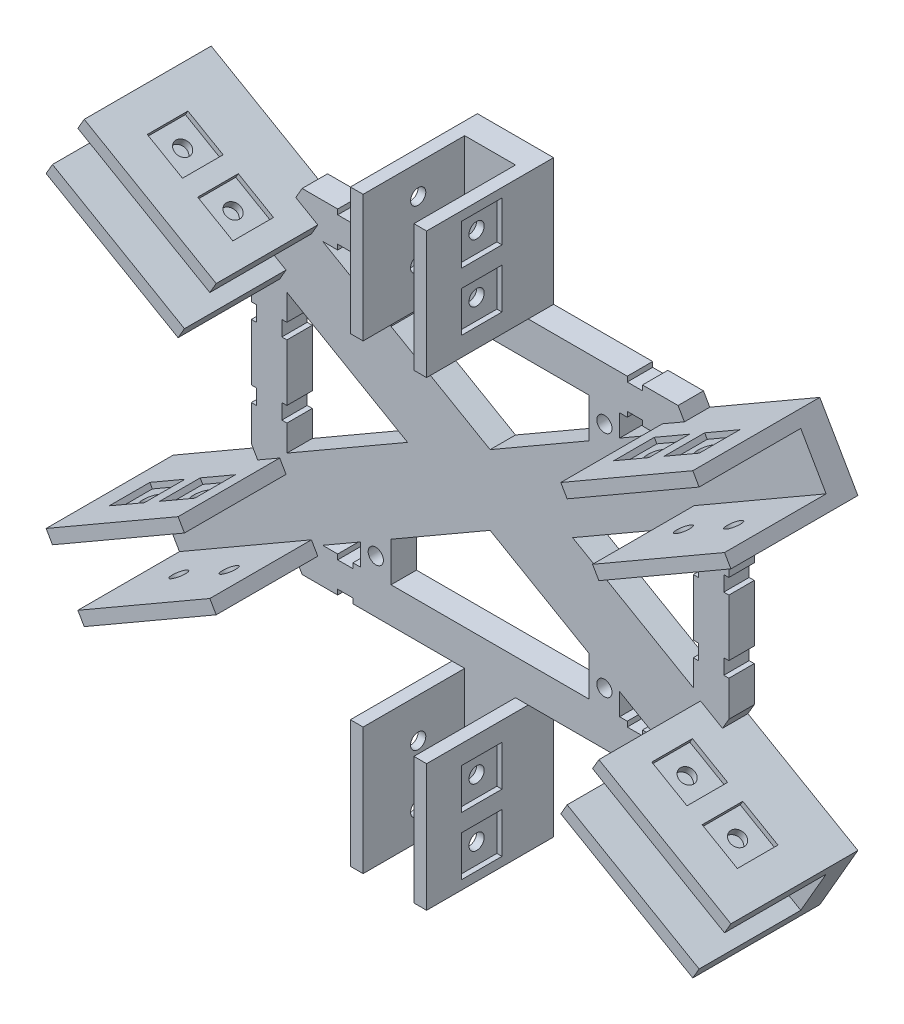
SolidWorks part; units mm, degrees
ref_plane "Plan de face" through (0, 0, 0) normal (0, 0, 1) x (1, 0, 0)
ref_plane "Plan de dessus" through (0, 0, 0) normal (0, 1, 0) x (1, 0, 0)
ref_plane "Plan de droite" through (0, 0, 0) normal (1, 0, 0) x (0, 0, -1)
sketch "Esquisse1" plane through (0, 0, 0) normal (0, 0, 1) x (1, 0, 0)
  line L1 (-27, -32.909) -> (-27, -31.909)
  line L2 (-27, -31.909) -> (-30, -31.909)
  line L3 (-30, -31.909) -> (-30, -32.909)
  line L4 (-30, -32.909) -> (-37, -32.909)
  line L5 (89.9983, 57.7339) -> (33.4379, 25.0787) construction
  line L6 (-47, -15.5885) -> (-47, -8.5885)
  line L7 (-47, -8.5885) -> (-46, -8.5885)
  line L8 (-46, -8.5885) -> (-46, -5.5885)
  line L9 (-46, -5.5885) -> (-47, -5.5885)
  line L10 (-47, -5.5885) -> (-47, 5.5885)
  line L11 (0, -32.909) -> (0, 32.909) construction
  line L12 (40, 0) -> (-40, 0) construction
  line L13 (-42, -24.2487) -> (0, 0) construction
  line L14 (-40, 5.5885) -> (-40, -5.5885)
  line L15 (-40, -5.5885) -> (-41, -5.5885)
  line L16 (-41, -5.5885) -> (-41, -8.5885)
  line L17 (-41, -8.5885) -> (-40, -8.5885)
  line L18 (-40, -8.5885) -> (-40, -13.7128)
  line L19 (40, 13.7128) -> (16.2487, 0)
  line L20 (-32.9585, -25.909) -> (-30, -25.909)
  line L21 (-30, -25.909) -> (-30, -26.909)
  line L22 (-30, -26.909) -> (-27, -26.909)
  line L23 (-27, -26.909) -> (-27, -25.909)
  line L24 (59.9007, 43.2438) -> (38.2501, 30.7438)
  line L25 (-42, 24.2487) -> (0, 0) construction
  line L26 (19.5, -25.909) -> (0, -25.909)
  line L27 (-27, 26.909) -> (-27, 25.909)
  line L28 (-30, 26.909) -> (-27, 26.909)
  line L29 (-30, 25.909) -> (-30, 26.909)
  line L30 (-32.9585, 25.909) -> (-30, 25.909)
  line L31 (-40, 13.7128) -> (-16.2487, 0)
  line L32 (-40, 8.5885) -> (-40, 13.7128)
  line L33 (-41, 8.5885) -> (-40, 8.5885)
  line L34 (-41, 5.5885) -> (-41, 8.5885)
  line L35 (-40, 5.5885) -> (-41, 5.5885)
  line L36 (-46, 5.5885) -> (-47, 5.5885)
  line L37 (-46, 8.5885) -> (-46, 5.5885)
  line L38 (-47, 8.5885) -> (-46, 8.5885)
  line L39 (-47, 15.5885) -> (-47, 8.5885)
  line L40 (-59.9007, 43.2438) -> (-38.2501, 30.7438)
  line L41 (-30, 32.909) -> (-37, 32.909)
  line L42 (-30, 31.909) -> (-30, 32.909)
  line L43 (-27, 31.909) -> (-30, 31.909)
  line L44 (-27, 32.909) -> (-27, 31.909)
  line L45 (-27, 32.909) -> (-7.5, 32.909)
  line L46 (42, 24.2487) -> (0, 0) construction
  line L47 (42, -24.2487) -> (0, 0) construction
  line L48 (27, 32.909) -> (27, 31.909)
  line L49 (27, 31.909) -> (30, 31.909)
  line L50 (30, 31.909) -> (30, 32.909)
  line L51 (30, 32.909) -> (37, 32.909)
  line L52 (-45.7501, 17.7534) -> (-47, 15.5885)
  line L53 (47, 15.5885) -> (47, 8.5885)
  line L54 (47, 8.5885) -> (46, 8.5885)
  line L55 (46, 8.5885) -> (46, 5.5885)
  line L56 (46, 5.5885) -> (47, 5.5885)
  line L57 (40, 5.5885) -> (41, 5.5885)
  line L58 (41, 5.5885) -> (41, 8.5885)
  line L59 (41, 8.5885) -> (40, 8.5885)
  line L60 (40, 8.5885) -> (40, 13.7128)
  line L61 (32.9585, 25.909) -> (25.5, 21.6028)
  line L62 (32.9585, 25.909) -> (30, 25.909)
  line L63 (30, 25.909) -> (30, 26.909)
  line L64 (30, 26.909) -> (27, 26.909)
  line L65 (27, 26.909) -> (27, 25.909)
  line L66 (27, -26.909) -> (27, -25.909)
  line L67 (30, -26.909) -> (27, -26.909)
  line L68 (30, -25.909) -> (30, -26.909)
  line L69 (32.9585, -25.909) -> (30, -25.909)
  line L70 (-32.9585, 25.909) -> (-25.5, 21.6028)
  line L71 (40, -8.5885) -> (40, -13.7128)
  line L72 (41, -8.5885) -> (40, -8.5885)
  line L73 (41, -5.5885) -> (41, -8.5885)
  line L74 (40, -5.5885) -> (41, -5.5885)
  line L75 (40, 5.5885) -> (40, -5.5885)
  line L76 (47, -5.5885) -> (47, 5.5885)
  line L77 (46, -5.5885) -> (47, -5.5885)
  line L78 (46, -8.5885) -> (46, -5.5885)
  line L79 (47, -8.5885) -> (46, -8.5885)
  line L80 (47, -15.5885) -> (47, -8.5885)
  line L81 (-37, 32.909) -> (-38.2501, 30.7438)
  line L82 (30, -32.909) -> (37, -32.909)
  line L83 (30, -31.909) -> (30, -32.909)
  line L84 (27, -31.909) -> (30, -31.909)
  line L85 (27, -32.909) -> (27, -31.909)
  line L86 (40, -13.7128) -> (16.2487, 0)
  line L87 (-25.5, 25.909) -> (-25.5, 21.6028)
  line L88 (-19.5, 25.909) -> (-19.5, 18.1387)
  line L89 (-40, -13.7128) -> (-16.2487, 0)
  line L90 (25.5, 25.909) -> (25.5, 21.6028)
  line L91 (19.5, 25.909) -> (19.5, 18.1387)
  line L92 (19.5, 18.1387) -> (0, 6.8803)
  line L93 (-19.5, 18.1387) -> (0, 6.8803)
  line L94 (-32.9585, -25.909) -> (-25.5, -21.6028)
  line L95 (-25.5, -25.909) -> (-25.5, -21.6028)
  line L96 (-19.5, -25.909) -> (-19.5, -18.1387)
  line L97 (-19.5, -18.1387) -> (0, -6.8803)
  line L98 (32.9585, -25.909) -> (25.5, -21.6028)
  line L99 (25.5, -25.909) -> (25.5, -21.6028)
  line L100 (19.5, -25.909) -> (19.5, -18.1387)
  line L101 (19.5, -18.1387) -> (0, -6.8803)
  line L102 (27, 25.909) -> (25.5, 25.909)
  line L103 (19.5, 25.909) -> (0, 25.909)
  line L104 (0, 25.909) -> (-19.5, 25.909)
  line L105 (-25.5, 25.909) -> (-27, 25.909)
  line L106 (0, -25.909) -> (-19.5, -25.909)
  line L107 (-25.5, -25.909) -> (-27, -25.909)
  line L108 (27, -25.909) -> (25.5, -25.909)
  line L109 (67.4007, 30.2534) -> (59.9007, 43.2438)
  line L110 (67.4007, 30.2534) -> (45.7501, 17.7534)
  line L111 (37, 32.909) -> (38.2501, 30.7438)
  line L112 (45.7501, 17.7534) -> (47, 15.5885)
  line L113 (-67.4007, 30.2534) -> (-45.7501, 17.7534)
  line L114 (-67.4007, 30.2534) -> (-59.9007, 43.2438)
  line L115 (-7.5, 32.909) -> (-7.5, 57.909)
  line L116 (-7.5, 57.909) -> (7.5, 57.909)
  line L117 (37, -32.909) -> (38.2501, -30.7438)
  line L118 (45.7501, -17.7534) -> (47, -15.5885)
  line L119 (67.4007, -30.2534) -> (45.7501, -17.7534)
  line L120 (67.4007, -30.2534) -> (59.9007, -43.2438)
  line L121 (59.9007, -43.2438) -> (38.2501, -30.7438)
  line L122 (-37, -32.909) -> (-38.2501, -30.7438)
  line L123 (-45.7501, -17.7534) -> (-47, -15.5885)
  line L124 (-67.4007, -30.2534) -> (-59.9007, -43.2438)
  line L125 (-67.4007, -30.2534) -> (-45.7501, -17.7534)
  line L126 (-59.9007, -43.2438) -> (-38.2501, -30.7438)
  line L127 (7.5, 57.909) -> (7.5, 32.909)
  line L128 (7.5, 32.909) -> (27, 32.909)
  line L129 (7.5, -32.909) -> (27, -32.909)
  line L130 (-27, -32.909) -> (-7.5, -32.909)
  line L131 (-7.5, -32.909) -> (-7.5, -57.909)
  line L132 (7.5, -57.909) -> (7.5, -32.909)
  line L133 (-7.5, -57.909) -> (7.5, -57.909)
  circle A0 centre (22.5, 22.5) radius 1.5
  circle A1 centre (-22.5, 22.5) radius 1.5
  circle A2 centre (22.5, -22.5) radius 1.5
  circle A3 centre (-22.5, -22.5) radius 1.5
  point P10 (-42, -24.2487)
  point P41 (-47, 0)
  point P73 (0, 25.909)
  point P74 (0, -25.909)
  point P75 (0, -25.909)
  point P94 (47, 0)
  dimension "D13" = 2
  dimension "D1" = 1
  dimension "D2" = 3
  dimension "D3" = 7
  dimension "D4" = 3
  dimension "D5" = 7
  dimension "D6" = 60
  dimension "D7" = 15
  dimension "D8" = 1
  dimension "D9" = 1
  dimension "D10" = 1
  dimension "D11" = 7
  dimension "D12" = 3
  dimension "D14" = 20
  dimension "D15" = 30
  dimension "D16" = 2
  dimension "D17" = 22.5
  dimension "D18" = 22.5
  dimension "D19" = 3
  dimension "D20" = 90
  dimension "D21" = 90
  dimension "D22" = 2.5
  dimension "D23" = 7.5
  dimension "D24" = 7.5
  dimension "D25" = 25
extrude "Boss.-Extru.2" add sketch "Esquisse1" along normal blind 5
sketch "Esquisse4" plane through (0, 0, 0) normal (0, 0, -1) x (-1, 0, 0)
  line L1 (-22.5, 20.1429) -> (-20.4587, 21.3214)
  line L2 (-20.4587, 21.3214) -> (-20.4587, 23.6786)
  line L3 (-20.4587, 23.6786) -> (-22.5, 24.8571)
  line L4 (-22.5, 24.8571) -> (-24.5413, 23.6786)
  line L5 (-24.5413, 23.6786) -> (-24.5413, 21.3214)
  line L6 (-24.5413, 21.3214) -> (-22.5, 20.1429)
  line L7 (0, -32.2873) -> (0, 32.2873) construction
  line L8 (43.6304, 0) -> (-43.6304, 0) construction
  line L9 (0, -32.909) -> (0, 32.909) construction
  line L10 (-40, 0) -> (40, 0) construction
  line L11 (24.5413, 21.3214) -> (22.5, 20.1429)
  line L12 (24.5413, 23.6786) -> (24.5413, 21.3214)
  line L13 (22.5, 24.8571) -> (24.5413, 23.6786)
  line L14 (20.4587, 23.6786) -> (22.5, 24.8571)
  line L15 (20.4587, 21.3214) -> (20.4587, 23.6786)
  line L16 (22.5, 20.1429) -> (20.4587, 21.3214)
  line L17 (22.5, -20.1429) -> (20.4587, -21.3214)
  line L18 (20.4587, -21.3214) -> (20.4587, -23.6786)
  line L19 (20.4587, -23.6786) -> (22.5, -24.8571)
  line L20 (22.5, -24.8571) -> (24.5413, -23.6786)
  line L21 (24.5413, -23.6786) -> (24.5413, -21.3214)
  line L22 (24.5413, -21.3214) -> (22.5, -20.1429)
  line L23 (-24.5413, -21.3214) -> (-22.5, -20.1429)
  line L24 (-24.5413, -23.6786) -> (-24.5413, -21.3214)
  line L25 (-22.5, -24.8571) -> (-24.5413, -23.6786)
  line L26 (-20.4587, -23.6786) -> (-22.5, -24.8571)
  line L27 (-20.4587, -21.3214) -> (-20.4587, -23.6786)
  line L28 (-22.5, -20.1429) -> (-20.4587, -21.3214)
  circle A0 centre (-22.5, 22.5) radius 2.0413 construction
  circle A1 centre (22.5, 22.5) radius 2.0413 construction
  circle A2 centre (22.5, -22.5) radius 2.0413 construction
  circle A3 centre (-22.5, -22.5) radius 2.0413 construction
extrude "Enlèv. mat.-Extru.2" cut sketch "Esquisse4" against normal blind 2
sketch "Esquisse5" plane through (63.6506, 36.7487, 0) normal (0.866, 0.5, 0) x (0, 0, -1)
  line L0 (-5, -7.5001) -> (-5, -5.0001)
  line L2 (-5, -5.0001) -> (-25, -5.0001)
  line L3 (-25, -5.0001) -> (-25, -7.5001)
  line L4 (-25, -7.5001) -> (-5, -7.5001)
  dimension "D1" = 20
  dimension "D2" = 2.5
extrude "Boss.-Extru.3" add sketch "Esquisse5" against normal blind 30
sketch "Esquisse7" plane through (63.6506, 36.7487, 0) normal (0.866, 0.5, 0) x (0, 0, -1)
  line L0 (-5, 4.9999) -> (-5, 7.4999)
  line L2 (-5, 7.4999) -> (-25, 7.4999)
  line L3 (-25, 7.4999) -> (-25, 4.9999)
  line L4 (-25, 4.9999) -> (-5, 4.9999)
  line L5 (-5, -5.0001) -> (-5, 7.4999) construction
  dimension "D1" = 20
  dimension "D2" = 2.5
extrude "Boss.-Extru.4" add sketch "Esquisse7" against normal blind 30
sketch "Esquisse8" plane through (3.7501, -6.4953, 0) normal (0.5, -0.866, 0) x (0.866, 0.5, 0)
  line L1 (47.611, 18.1555) -> (55.611, 18.1555)
  line L2 (47.611, 18.1555) -> (47.611, 10.1555)
  line L3 (47.611, 10.1555) -> (55.611, 10.1555)
  line L4 (55.611, 18.1555) -> (55.611, 10.1555)
  dimension "D1" = 8
  dimension "D2" = 8
extrude "Enlèv. mat.-Extru.3" cut sketch "Esquisse8" against normal blind 1
sketch "Esquisse9" plane through (3.7501, -6.4953, 0) normal (0.5, -0.866, 0) x (0.866, 0.5, 0)
  line L0 (55.611, 18.1555) -> (47.611, 18.1555) construction
  line L1 (59.0628, 18.1555) -> (67.0628, 18.1555)
  line L2 (59.0628, 18.1555) -> (59.0628, 10.1555)
  line L3 (59.0628, 10.1555) -> (67.0628, 10.1555)
  line L4 (67.0628, 18.1555) -> (67.0628, 10.1555)
  dimension "D1" = 8
  dimension "D2" = 8
extrude "Enlèv. mat.-Extru.4" cut sketch "Esquisse9" against normal blind 1
ref_plane "Plan8" through (0.0001, -0.0001, 0) normal (-0.5, 0.866, 0) x (-0.866, -0.5, 0)
sketch "Esquisse10" plane through (3.2501, -5.6293, 0) normal (0.5, -0.866, 0) x (0.866, 0.5, 0)
  line L3 (55.611, 18.1555) -> (47.611, 18.1555) construction
  line L4 (47.611, 18.1555) -> (47.611, 10.1555) construction
  circle A0 centre (51.611, 14.1555) radius 1.5
  point P2 (51.611, 18.1555)
  point P3 (47.611, 14.1555)
extrude "Enlèv. mat.-Extru.5" cut sketch "Esquisse10" against normal blind 3
ref_plane "Plan9" through (49.6552, 28.6684, 0) normal (-0.866, -0.5, 0) x (0, 0, 1)
mirror "Symétrie4" about plane through (49.6552, 28.6684, 0) normal (-0.866, -0.5, 0) of "Enlèv. mat.-Extru.5"
mirror "Symétrie5" about plane through (0.0001, -0.0001, 0) normal (-0.5, 0.866, 0) of "Enlèv. mat.-Extru.3", "Enlèv. mat.-Extru.4", "Enlèv. mat.-Extru.5", "Symétrie4"
mirror "Symétrie7" about plane through (0, 0, 0) normal (0, 1, 0) of "Boss.-Extru.3", "Boss.-Extru.4", "Enlèv. mat.-Extru.3", "Enlèv. mat.-Extru.4", "Enlèv. mat.-Extru.5", "Symétrie4", "Symétrie5"
mirror "Symétrie8" about plane through (0, 0, 0) normal (1, 0, 0) of "Boss.-Extru.3", "Boss.-Extru.4", "Enlèv. mat.-Extru.3", "Enlèv. mat.-Extru.4", "Symétrie5", "Symétrie4", "Enlèv. mat.-Extru.5", "Symétrie7"
sketch "Esquisse11" plane through (0, 57.909, 0) normal (0, 1, 0) x (1, 0, 0)
  line L6 (-7.5, -5) -> (-5, -5)
  line L7 (-7.5, -5) -> (-7.5, -25)
  line L8 (-7.5, -25) -> (-5, -25)
  line L9 (-5, -5) -> (-5, -25)
  dimension "D1" = 2.5
  dimension "D2" = 20
extrude "Boss.-Extru.5" add sketch "Esquisse11" against normal blind 25
sketch "Esquisse50" plane through (-7.5, 26.5177, -42.9653) normal (-1, 0, 0) x (0, 0, 1)
  line L0 (42.9653, 31.3912) -> (42.9653, 6.3912) construction
  line L1 (53.1253, 18.1555) -> (61.1253, 18.1555)
  line L2 (53.1253, 18.1555) -> (53.1253, 10.1555)
  line L3 (53.1253, 10.1555) -> (61.1253, 10.1555)
  line L4 (61.1253, 18.1555) -> (61.1253, 10.1555)
  dimension "D1" = 8
  dimension "D2" = 8
  dimension "D3" = 10.16
extrude "Enlèv. mat.-Extru.25" cut sketch "Esquisse50" against normal blind 1
sketch "Esquisse52" plane through (-7.5, 26.5177, -42.9653) normal (-1, 0, 0) x (0, 0, 1)
  line L0 (53.1253, 18.1555) -> (53.1253, 10.1555) construction
  line L1 (53.1253, 29.6055) -> (61.1253, 29.6055)
  line L2 (53.1253, 29.6055) -> (53.1253, 21.6055)
  line L3 (53.1253, 21.6055) -> (61.1253, 21.6055)
  line L4 (61.1253, 29.6055) -> (61.1253, 21.6055)
  line L6 (61.1253, 18.1555) -> (53.1253, 18.1555) construction
  dimension "D1" = 8
  dimension "D2" = 8
  dimension "D3" = 3.45
extrude "Enlèv. mat.-Extru.26" cut sketch "Esquisse52" against normal blind 1
sketch "Esquisse54" plane through (-6.5, 26.5177, -42.9653) normal (-1, 0, 0) x (0, 0, 1)
  line L3 (61.1253, 18.1555) -> (53.1253, 18.1555) construction
  line L4 (53.1253, 18.1555) -> (53.1253, 10.1555) construction
  circle A0 centre (57.1253, 14.1555) radius 1.5
  point P2 (57.1253, 18.1555)
  point P3 (53.1253, 14.1555)
extrude "Enlèv. mat.-Extru.27" cut sketch "Esquisse54" against normal blind 3
ref_plane "Plan14" through (0, 46.3982, 0) normal (0, 1, 0) x (-1, 0, 0)
mirror "Symétrie9" about plane through (0, 46.3982, 0) normal (0, 1, 0) of "Enlèv. mat.-Extru.27"
ref_plane "Plan17" through (0, 0, 0) normal (-1, 0, 0) x (0, 0, 1)
mirror "Symétrie10" about plane through (0, 0, 0) normal (-1, 0, 0) of "Symétrie9", "Enlèv. mat.-Extru.27", "Enlèv. mat.-Extru.26", "Enlèv. mat.-Extru.25", "Boss.-Extru.5"
mirror "Symétrie11" about plane through (0, 0, 0) normal (0, 1, 0) of "Symétrie10", "Symétrie9", "Enlèv. mat.-Extru.27", "Enlèv. mat.-Extru.26", "Enlèv. mat.-Extru.25", "Boss.-Extru.5"
